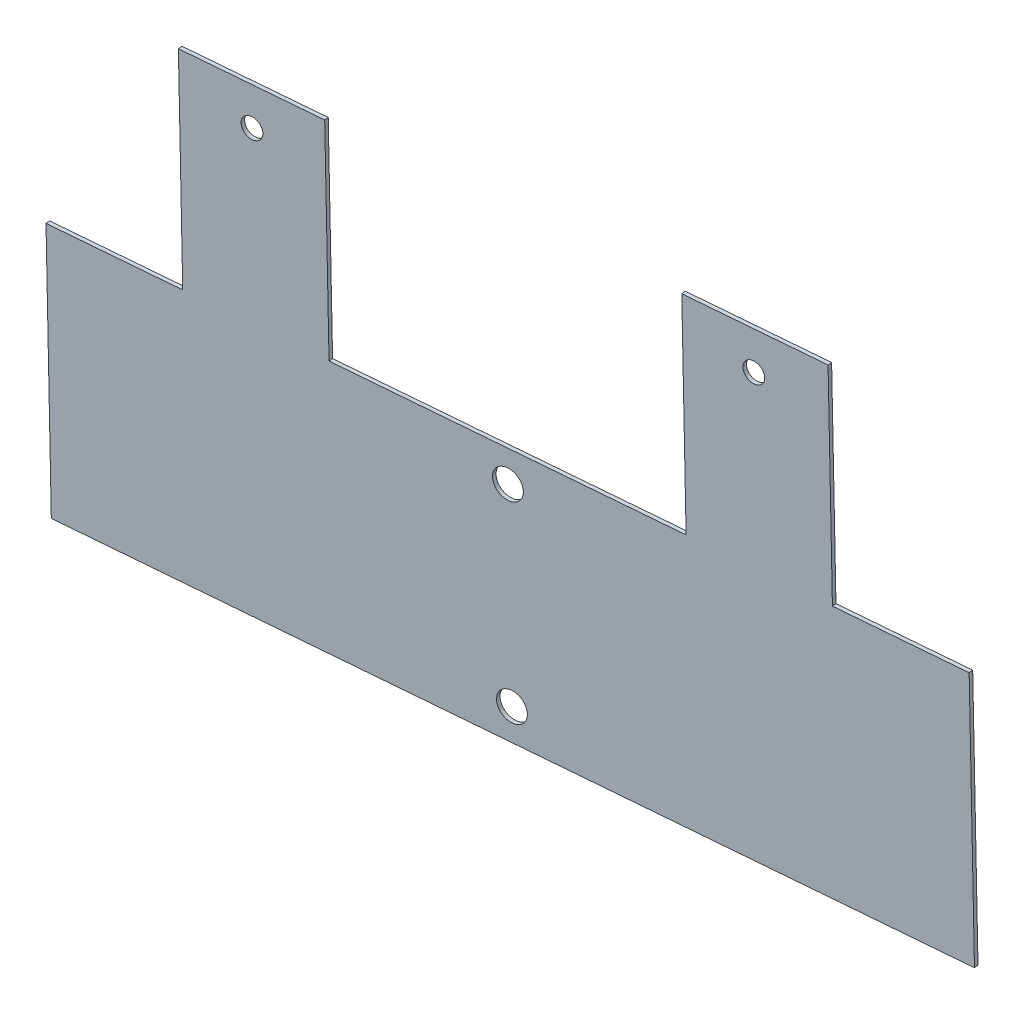
SolidWorks part; units mm, degrees
ref_plane "Front Plane" through (0, 0, 0) normal (0, 0, 1) x (1, 0, 0)
ref_plane "Top Plane" through (0, 0, 0) normal (0, 1, 0) x (1, 0, 0)
ref_plane "Right Plane" through (0, 0, 0) normal (1, 0, 0) x (0, 0, -1)
sketch "Sketch1" plane through (16.9972, -4.1499, 204.6314) normal (-0.0828, 0.0202, -0.9964) x (0.9966, 0.002, -0.0827)
  line L0 (-405.6316, 283.217) -> (-385.6926, 283.217)
  line L1 (-520.3126, 323.857) -> (-500.3736, 323.857)
  line L2 (-520.3126, 323.857) -> (-520.3126, 283.217)
  line L3 (-520.3126, 283.217) -> (-500.3736, 283.217)
  line L4 (-385.6926, 323.857) -> (-385.6926, 283.217)
  line L6 (-426.9676, 283.217) -> (-426.9676, 250.0037)
  line L7 (-426.9676, 250.0037) -> (-405.6316, 250.0037)
  line L8 (-405.6316, 283.217) -> (-405.6316, 250.0037)
  line L9 (-405.0144, 323.857) -> (-385.6926, 323.857)
  line L14 (-479.4985, 323.857) -> (-465.3599, 323.857)
  line L20 (-500.3736, 283.217) -> (-500.3736, 250.0037)
  line L21 (-500.3736, 250.0037) -> (-479.0376, 250.0037)
  line L22 (-479.0376, 283.217) -> (-479.0376, 250.0037)
  line L23 (-479.0376, 283.217) -> (-426.9676, 283.217)
  line L24 (-432.4144, 323.857) -> (-405.0144, 323.857)
  line L25 (-500.3736, 323.857) -> (-479.4985, 323.857)
  line L26 (-445.0971, 323.857) -> (-432.4144, 323.857)
  line L31 (-465.3599, 323.857) -> (-445.0971, 323.857)
  dimension "D1" = 134.62
  dimension "D2" = 40.64
  dimension "D3" = 21.336
  dimension "D4" = 52.07
  dimension "D5" = 33.2133
extrude "Boss-Extrude1" add sketch "Sketch1" along normal blind 0.6096
ref_plane "Plane1" through (-508.5923, -1, 42.2247) normal (0.9966, 0.002, -0.0827) x (-0.0828, 0.028, -0.9962)
sketch "Sketch5" plane through (16.9468, -4.1376, 204.024) normal (-0.0828, 0.0202, -0.9964) x (-0.9966, -0.0017, 0.0827)
  circle A1 centre (452.9566, -318.9845) radius 2.25
extrude "Cut-Extrude2" cut sketch "Sketch5" against normal up to surface (0.6096 mm away) up to face at (-434.373, -283.8993, 236.4501)
ref_plane "Plane2" through (0.0852, -303.4744, -6.1615) normal (0.0003, -0.9998, -0.0203) x (-1, -0.0003, 0)
mirror "Mirror1" about plane through (0.0852, -303.4744, -6.1615) normal (0.0003, -0.9998, -0.0203) of "Cut-Extrude2"
sketch "Sketch6" plane through (16.9468, -4.1376, 204.024) normal (-0.0828, 0.0202, -0.9964) x (-0.9966, -0.0017, 0.0827)
  circle A1 centre (416.5068, -256.1738) radius 1.5875
  dimension "D1" = 3.175
  dimension "D2" = 103.726
  dimension "D3" = 6.0353
extrude "Cut-Extrude5" cut sketch "Sketch6" against normal up to surface (0.6096 mm away) up to face at (-436.6564, -293.1953, 236.4512)
ref_plane "Plane3" through (-451.4485, -0.8877, 37.4805) normal (-0.9966, -0.002, 0.0827) x (0.0827, 0.0002, 0.9966)
sketch "Sketch7" plane through (16.9468, -4.1376, 204.024) normal (-0.0828, 0.0202, -0.9964) x (-0.9966, -0.0017, 0.0827)
  circle A0 centre (489.6815, -256.1944) radius 1.5875
  dimension "D1" = 3.175
  dimension "D2" = 10.7236
  dimension "D3" = 6.0559
extrude "Cut-Extrude6" cut sketch "Sketch7" against normal up to surface (0.6096 mm away) up to face at (-399.6628, -260.97, 234.0319)
